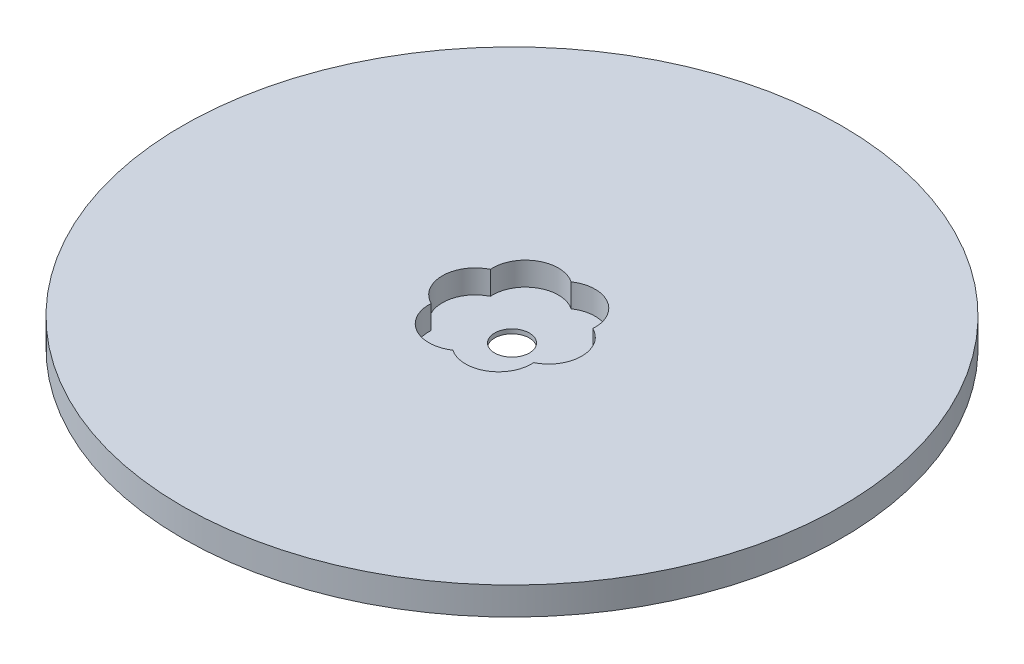
SolidWorks part; units mm, degrees
ref_plane "Front Plane" through (0, 0, 0) normal (0, 0, 1) x (1, 0, 0)
ref_plane "Top Plane" through (0, 0, 0) normal (0, 1, 0) x (1, 0, 0)
ref_plane "Right Plane" through (0, 0, 0) normal (1, 0, 0) x (0, 0, -1)
sketch "Sketch1" plane through (0, 0, 0) normal (0, 1, 0) x (1, 0, 0)
  circle A0 centre (0, 0) radius 95
  dimension "FLANGE_OD" = 190
extrude "Boss-Extrude1" add sketch "Sketch1" along normal blind 8
sketch "Sketch2" plane through (0, 0, 0) normal (0, 1, 0) x (1, 0, 0)
  circle A0 centre (0, 0) radius 5
  dimension "BORE_D" = 10
extrude "Cut-Extrude1" cut sketch "Sketch2" along normal through all
sketch "Sketch3" plane through (0, 8, 0) normal (0, 1, 0) x (1, 0, 0)
  circle A0 centre (0, 0) radius 10.5917 construction
  circle A1 centre (-10.5917, 0) radius 9.4984
  dimension "BOLT_D" = 18.9969
  dimension "BOLT_PCD" = 21.1833
extrude "Cut-Extrude2" cut sketch "Sketch3" against normal blind 6.744
pattern_circular "CirPattern1" count 6 over 360 about axis through (0, 0, 0) along (0, 1, 0) of "Cut-Extrude2"
